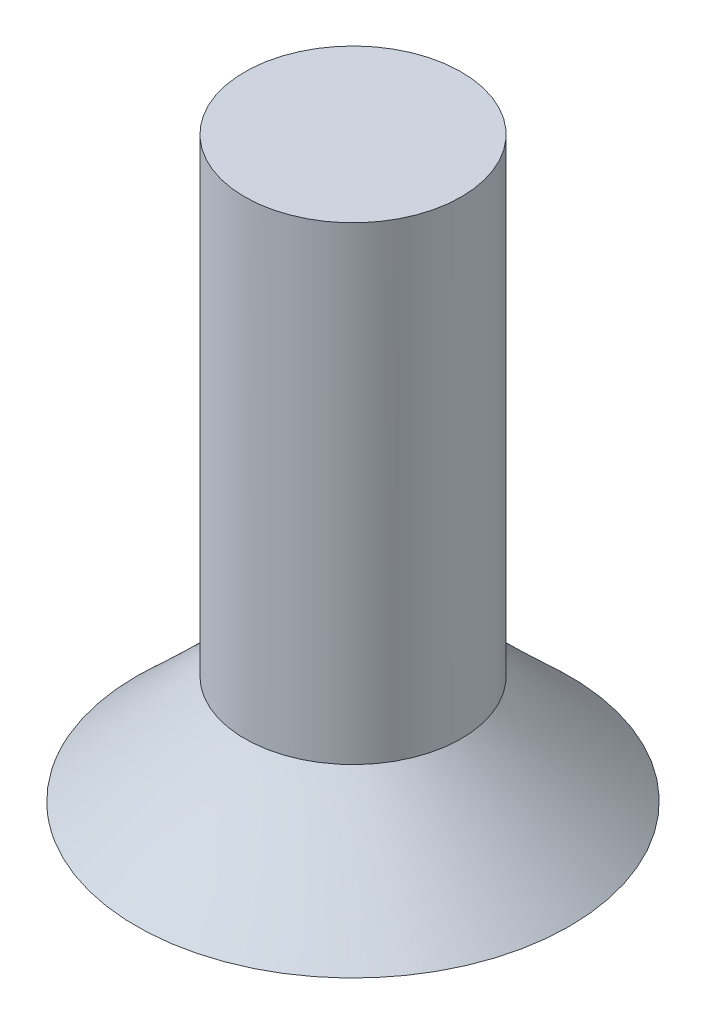
SolidWorks part; units mm, degrees
ref_plane "Ön Düzlem" through (0, 0, 0) normal (0, 0, 1) x (1, 0, 0)
ref_plane "Üst Düzlem" through (0, 0, 0) normal (0, 1, 0) x (1, 0, 0)
ref_plane "Sağ Düzlem" through (0, 0, 0) normal (1, 0, 0) x (0, 0, -1)
sketch "Sketch1" plane through (0, 0, 0) normal (0, 1, 0) x (1, 0, 0)
  circle A0 centre (0, 0) radius 3
  dimension "D1" = 6
ref_plane "Plane1" through (0, 1.5, 0) normal (0, 1, 0) x (1, 0, 0)
sketch "Sketch2" plane through (0, 1.5, 0) normal (0, 1, 0) x (1, 0, 0)
  circle A0 centre (0, 0) radius 1.5
  dimension "D1" = 3
loft "Loft1" add profiles "Sketch1", "Sketch2" connector at (2.28, 0, -1.9498) connector at (0.6944, 1.5, -1.3296)
sketch "Sketch9" plane through (0, 1.5, 0) normal (0, 1, 0) x (1, 0, 0)
  circle A0 centre (0, 0) radius 1.5
extrude "Boss-Extrude1" add sketch "Sketch9" along normal blind 6.5
sketch "Sketch10" plane through (0, 0, 0) normal (0, -1, 0) x (-1, 0, 0)
  line L1 (-1.4434, 0) -> (-0.7217, -1.25)
  line L2 (-0.7217, -1.25) -> (0.7217, -1.25)
  line L3 (0.7217, -1.25) -> (1.4434, 0)
  line L4 (1.4434, 0) -> (0.7217, 1.25)
  line L5 (0.7217, 1.25) -> (-0.7217, 1.25)
  line L6 (-0.7217, 1.25) -> (-1.4434, 0)
  circle A0 centre (0, 0) radius 1.25 construction
  dimension "D1" = 2.5
extrude "Cut-Extrude1" cut sketch "Sketch10" against normal blind 1
